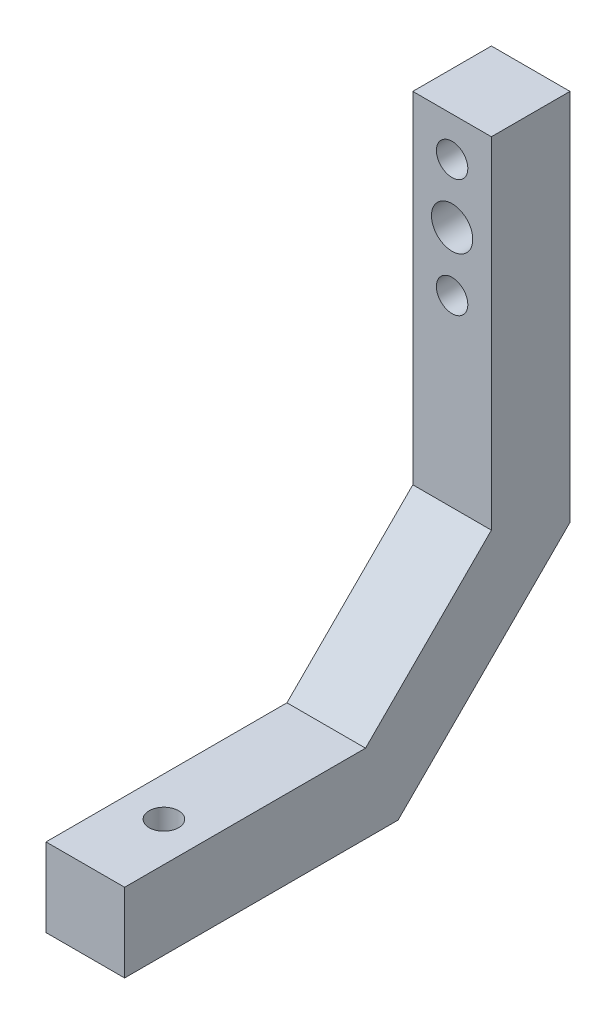
SolidWorks part; units mm, degrees
ref_plane "Front Plane" through (0, 0, 0) normal (0, 0, 1) x (1, 0, 0)
ref_plane "Top Plane" through (0, 0, 0) normal (0, 1, 0) x (1, 0, 0)
ref_plane "Right Plane" through (0, 0, 0) normal (1, 0, 0) x (0, 0, -1)
ref_axis "Z" through (0, 0, 47.607) along (0, 0, -1)
sketch "Sketch1" plane through (0, 0, 0) normal (1, 0, 0) x (0, 0, -1)
  line L0 (-8, 10) -> (0, 10)
  line L1 (0, 10) -> (0, -28)
  line L2 (0, -28) -> (-17.5, -45.5)
  line L3 (-17.5, -45.5) -> (-37.34, -45.5)
  line L4 (-37.34, -45.5) -> (-37.34, -37.5) construction
  line L5 (-37.34, -37.5) -> (-20.8137, -37.5)
  line L6 (-20.8137, -37.5) -> (-8, -24.6863)
  line L7 (-8, -24.6863) -> (-8, 10)
  line L8 (-13.4134, -30.0997) -> (-7.7566, -35.7566) construction
  line L10 (-37.34, -37.5) -> (-45.34, -37.5)
  line L11 (-37.34, -37.5) -> (-37.34, -45.5) construction
  line L12 (-37.34, -45.5) -> (-45.34, -45.5)
  line L13 (-45.34, -37.5) -> (-45.34, -45.5)
  dimension "D1" = 8
  dimension "D2" = 37.34
  dimension "D3" = 45.5
  dimension "D4" = 10
  dimension "D5" = 135
  dimension "D6" = 17.5
  dimension "D7" = 8
extrude "Boss-Extrude1" add sketch "Sketch1" along normal blind 4 and the other way blind 4
sketch "Sketch3" plane through (0, -37.5, 0) normal (0, 1, 0) x (1, 0, 0)
  line L0 (-55, 0) -> (55, 0) construction
  line L1 (0, -55) -> (0, 55) construction
  circle A0 centre (0, -37.34) radius 1.5
  dimension "D2" = 3
  dimension "D1" = 37.34
extrude "Cut-Extrude1" cut sketch "Sketch3" against normal through all
sketch "Sketch4" plane through (0, 0, 8) normal (0, 0, 1) x (1, 0, 0)
  line L0 (0, -6) -> (0, 6) construction
  circle A0 centre (0, 0) radius 2.1
  circle A1 centre (0, 6) radius 1.6
  circle A2 centre (0, -6) radius 1.6
  dimension "D1" = 4.2
  dimension "D3" = 3.2
  dimension "D2" = 12
extrude "Cut-Extrude2" cut sketch "Sketch4" against normal through all
ref_axis "Axis1" through (0, -37.5, 37.34) along (0, 1, 0)
equation "\"rbracket-width\"= 8"
equation "\"D1@Boss-Extrude1\"=\"rbracket-width\"/2"
equation "\"D2@Boss-Extrude1\"=\"rbracket-width\"/2"
equation "\"EyeCaptureRadius\"= ( \"EyeDiameter\" + \"EyeClearance\" ) / 2"
equation "\"rbracket_planetocenterline_dist\"= \"BasePlaneDistance\""
equation "\"D2@Sketch1\"=\"rbracket_planetocenterline_dist\""
equation "\"EyeDiameter\" = 35"
equation "\"BasePlaneDistance\" = \"EyeDiameter\"/2+19.84"
equation "\"EyeClearance\" = 2"
equation "\"D1@Sketch1\"=\"rbracket-width\""
equation "\"D3@Sketch1\"=(\"EyeDiameter\"+\"EyeClearance\"+\"EyeClearance\")/2 + \"L2Thickness\" + \"rbracket-width\" + \"L2Thickness\" + \"EyeClearance\""
equation "\"D4@Sketch1\"= 10"
equation "\"D6@Sketch1\"=\"EyeDiameter\"/2"
equation "\"D7@Sketch1\"=\"rbracket-width\""
equation "\"D1@Sketch3\"=\"BasePlaneDistance\""
equation "\"L2Thickness\" = 8"
